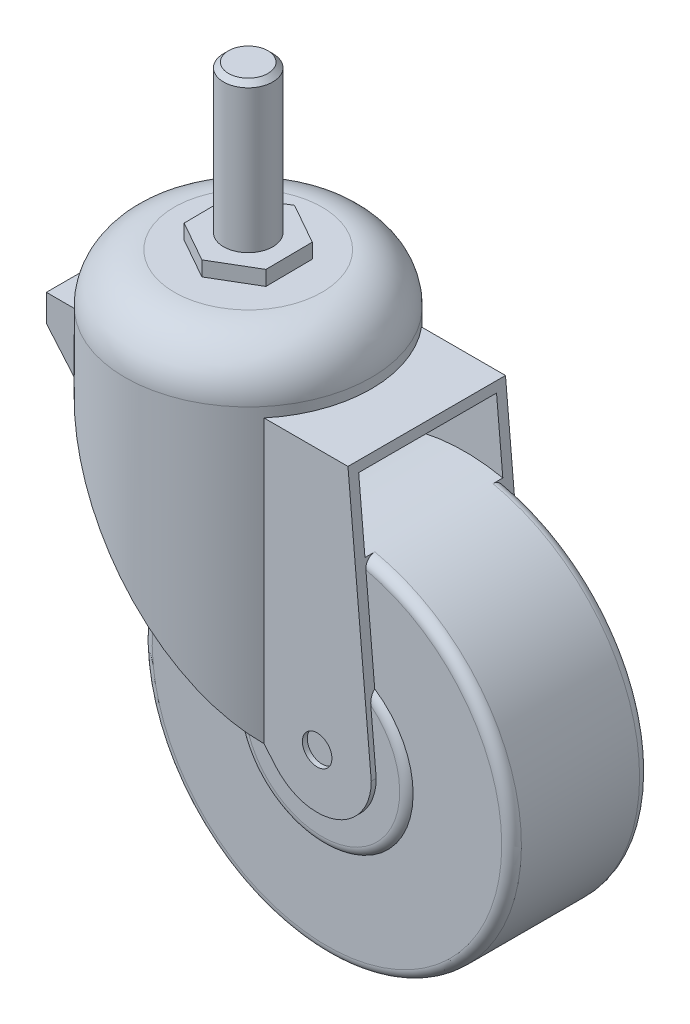
SolidWorks part; units mm, degrees
ref_plane "Спереди" through (0, 0, 0) normal (0, 0, 1) x (1, 0, 0)
ref_plane "Сверху" through (0, 0, 0) normal (0, 1, 0) x (1, 0, 0)
ref_plane "Справа" through (0, 0, 0) normal (1, 0, 0) x (0, 0, -1)
sketch "Эскиз1" plane through (0, 0, 0) normal (0, 0, 1) x (1, 0, 0)
  line L0 (0, 43.8734) -> (0, -46.9816) construction
  line L1 (30, 34.3097) -> (30, -53.9152) construction
  line L2 (-25, 8.6977) -> (25, 8.6977)
  line L3 (-20.3425, -44.3023) -> (72.1861, -44.3023) construction
  line L4 (25, 8.6977) -> (36.2619, 8.6977)
  line L5 (36.2619, 8.6977) -> (41, -44.3023)
  line L6 (-25, 8.6977) -> (-25, 3.221)
  line L7 (-25, 3.221) -> (21.6314, -51.4414)
  arc A0 (21.6314, -51.4414) -> (41, -44.3023) centre (30, -44.3023) ccw
  circle A1 centre (30, -44.3023) radius 3
  dimension "D5" = 22
  dimension "D6" = 6
  dimension "D1" = 30
  dimension "D2" = 50
  dimension "D3" = 25
  dimension "D4" = 53
sheet metal parameters "Листовой металл1" thickness 32 parameters "D1"=1.1, "Толщина"=32
base flange "Базовая кромка1" sketch "Эскиз1" thickness 32 reverse thickness direction no parameters "D1"=1.1
sketch "Эскиз4" plane through (0, 0, 0) normal (1, 0, 0) x (0, 0, -1)
  line L0 (32, -44.3023) -> (32, 8.6977) construction
  line L1 (2, 6.6977) -> (30, 6.6977)
  line L2 (2, 6.6977) -> (2, -61.0924)
  line L3 (2, -61.0924) -> (30, -61.0924)
  line L4 (30, 6.6977) -> (30, -61.0924)
  line L5 (0, -44.3023) -> (0, 8.6977) construction
  line L6 (32, 8.6977) -> (0, 8.6977) construction
  dimension "D1" = 2
  dimension "D2" = 2
  dimension "D3" = 2
extrude "Вырез-Вытянуть1" cut sketch "Эскиз4" against normal blind 56 and the other way blind 109 normal cut yes
sketch "Эскиз5" plane through (0, 8.6977, 0) normal (0, 1, 0) x (1, 0, 0)
  line L0 (0.0019, 42.2537) -> (0.0019, -5.8061) construction
  line L1 (36.2619, 32) -> (36.2619, 0) construction
  line L2 (-25, 16) -> (36.2619, 16) construction
  line L3 (-25, 32) -> (-25, 0) construction
  circle A0 centre (0.0019, 16) radius 25
  dimension "D2" = 50
  dimension "D1" = 36.26
extrude "Бобышка-Вытянуть1" add sketch "Эскиз5" along normal blind 12
fillet "Скругление2" radius 10 1 edges at (0.0019, 20.6977, 9)
sketch "Эскиз6" plane through (0, 8.6977, 0) normal (0, -1, 0) x (1, 0, 0)
  line L0 (-19.2075, 0) -> (19.2113, 0)
  line L1 (-25, 0) -> (21.6314, 0) construction
  line L2 (-19.2075, -32) -> (19.2113, -32)
  arc A0 (-19.2075, -32) -> (19.2113, -32) centre (0.0019, -16) ccw
  arc A1 (19.2113, 0) -> (-19.2075, 0) centre (0.0019, -16) ccw
extrude "Бобышка-Вытянуть2" add sketch "Эскиз6" along normal up to surface (12.2668 mm away) up to face at (-1.6843, -24.1102, -1)
sketch "Эскиз7" plane through (0, 6.6977, 0) normal (0, -1, 0) x (1, 0, 0)
  circle A0 centre (0.0019, -16) radius 23.2109
extrude "Вырез-Вытянуть2" cut sketch "Эскиз7" along normal blind 96 normal cut yes
sketch "Эскиз8" plane through (0, 20.6977, 0) normal (0, 1, 0) x (1, 0, 0)
  line L1 (8.2733, 11.3274) -> (8.1842, 20.827)
  line L2 (8.1842, 20.827) -> (-0.0872, 25.4996)
  line L3 (-0.0872, 25.4996) -> (-8.2695, 20.6726)
  line L4 (-8.2695, 20.6726) -> (-8.1804, 11.173)
  line L5 (-8.1804, 11.173) -> (0.091, 6.5004)
  line L6 (0.091, 6.5004) -> (8.2733, 11.3274)
  circle A0 centre (0.0019, 16) radius 9.5 construction
extrude "Бобышка-Вытянуть3" add sketch "Эскиз8" along normal blind 3
sketch "Эскиз9" plane through (0, 23.6977, 0) normal (0, 1, 0) x (1, 0, 0)
  circle A0 centre (0.0019, 16) radius 5
  dimension "D1" = 10
extrude "Бобышка-Вытянуть4" add sketch "Эскиз9" along normal blind 30
chamfer "Фаска1" distance 1 angle 45 1 edges at (0.0019, 53.6977, -11)
sketch "Эскиз10" plane through (0, 0, -30) normal (0, 0, 1) x (1, 0, 0)
  circle A0 centre (30, -44.3023) radius 37.5
  dimension "D1" = 75
extrude "Бобышка-Вытянуть5" add sketch "Эскиз10" along normal up to surface (28 mm away) up to face at (30, -41.3023, -2)
fillet "Скругление5" radius 2 2 edges at (31.9478, -81.7517, -30) (31.9478, -81.7517, -2)
sketch "Эскиз11" plane through (0, 0, -2) normal (0, 0, 1) x (1, 0, 0)
  circle A0 centre (30, -44.3023) radius 17.5
  dimension "D1" = 35
extrude "Бобышка-Вытянуть6" add sketch "Эскиз11" along normal blind 1
fillet "Скругление6" radius 2 1 edges at (31.6676, -61.7227, -1)
sketch "Эскиз12" plane through (0, 0, -30) normal (0, 0, -1) x (-1, 0, 0)
  circle A0 centre (-30, -44.3023) radius 17.5
  dimension "D1" = 35
extrude "Бобышка-Вытянуть7" add sketch "Эскиз12" along normal blind 1
fillet "Скругление7" radius 2 1 edges at (31.6676, -61.7227, -31)
flat pattern "Развертка1" [suppressed]
sketch "Сгиб-Линии1" plane through (0, 0, 0) normal (0, 1, 0) x (1, 0, 0)
sketch3d "Граничная рамка1" [suppressed]
  line L0 (55, 53, 0) -> (-11, 53, 0) construction
  line L1 (55, -11, 0) -> (-11, -11, 0) construction
  line L2 (55, 53, 0) -> (55, -11, 0) construction
  line L3 (-11, 53, 0) -> (-11, -11, 0) construction
